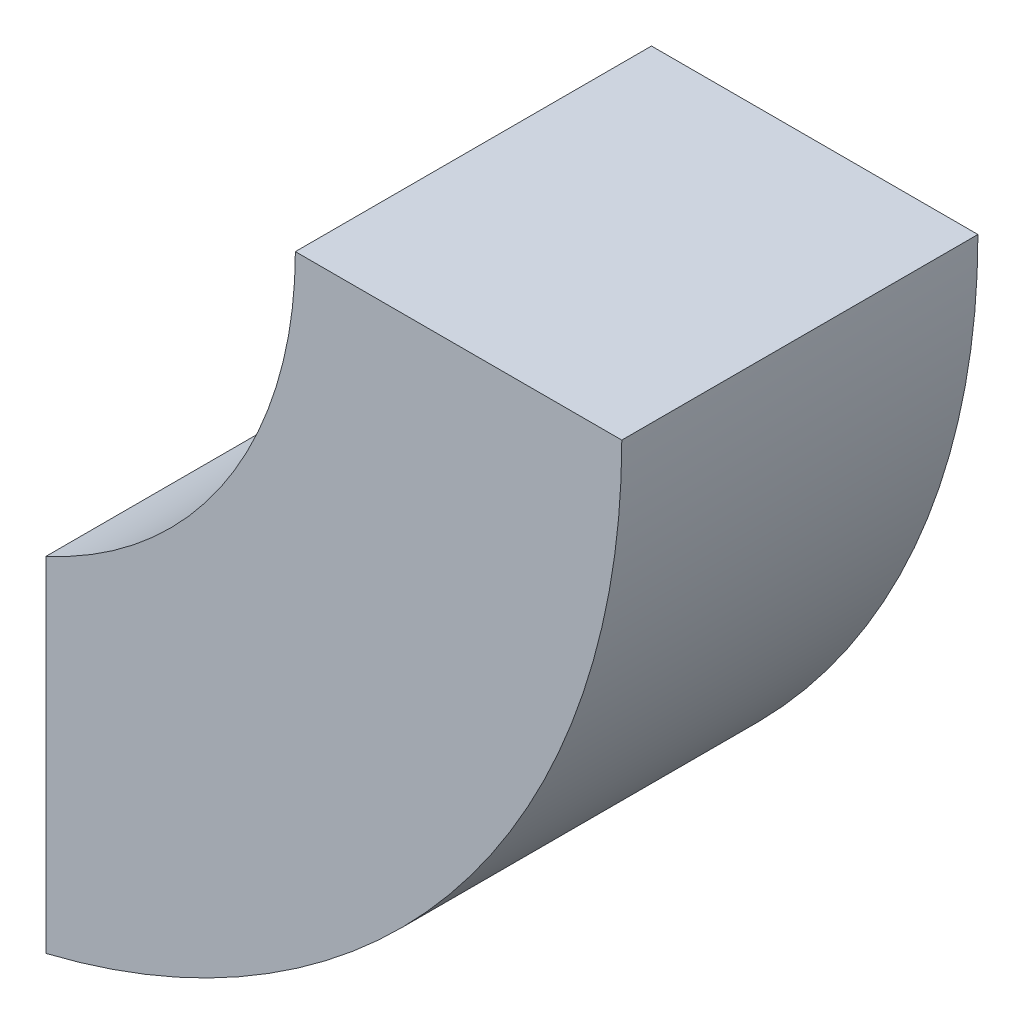
SolidWorks part; units mm, degrees
ref_plane "Front Plane" through (0, 0, 0) normal (0, 0, 1) x (1, 0, 0)
ref_plane "Top Plane" through (0, 0, 0) normal (0, 1, 0) x (1, 0, 0)
ref_plane "Right Plane" through (0, 0, 0) normal (1, 0, 0) x (0, 0, -1)
sketch "Sketch1" plane through (0, 0, 0) normal (0, 0, 1) x (1, 0, 0)
  line L0 (36, 0) -> (63.5, 0)
  line L1 (15, -61.7029) -> (15, -32.7261)
  arc A0 (36, 0) -> (15, -32.7261) centre (0, 0) cw
  arc A1 (63.5, 0) -> (15, -61.7029) centre (0, 0) cw
  dimension "D1" = 36
  dimension "D2" = 63.5
  dimension "D3" = 15
extrude "Boss-Extrude1" add sketch "Sketch1" along normal blind 30
